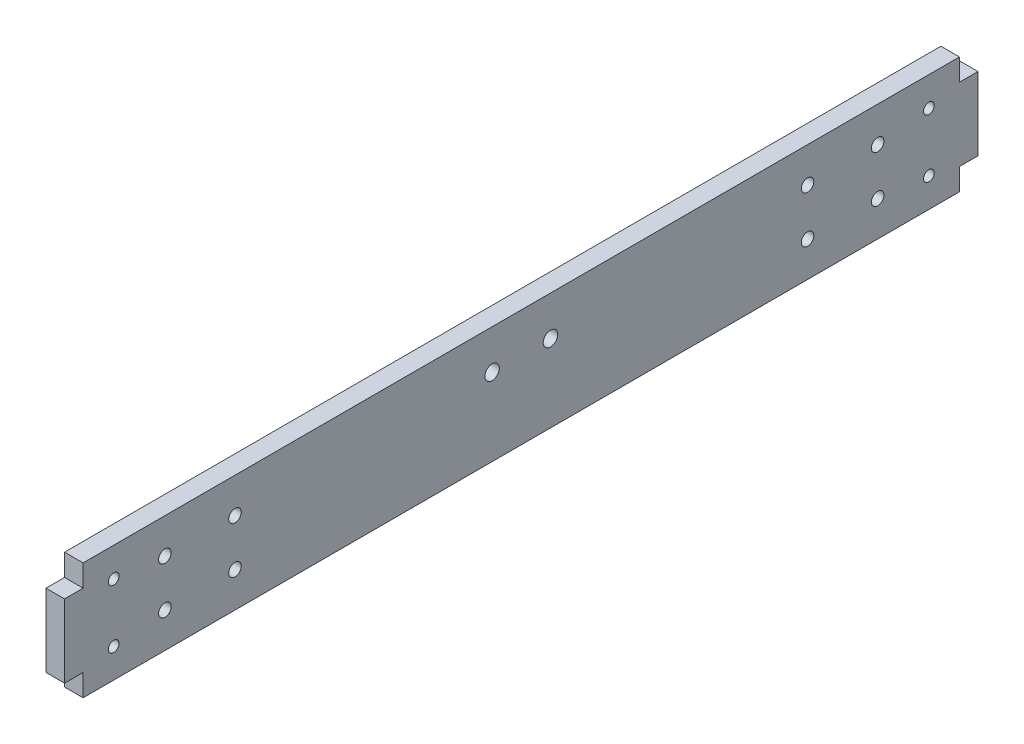
SolidWorks part; units mm, degrees
ref_plane "Front Plane" through (0, 0, 0) normal (0, 0, 1) x (1, 0, 0)
ref_plane "Top Plane" through (0, 0, 0) normal (0, 1, 0) x (1, 0, 0)
ref_plane "Right Plane" through (0, 0, 0) normal (1, 0, 0) x (0, 0, -1)
sketch "Sketch1" plane through (0, 0, 0) normal (1, 0, 0) x (0, 0, -1)
  line L0 (-150, -20) -> (-150, 20)
  line L1 (-150, -20) -> (150, -20)
  line L2 (-150, 20) -> (150, 20)
  line L3 (150, -20) -> (150, 20)
  line L4 (-150, -20) -> (150, 20) construction
  line L5 (-150, 20) -> (150, -20) construction
  point P1 (0, 0)
  dimension "D1" = 300
  dimension "D2" = 40
extrude "Boss-Extrude1" add sketch "Sketch1" along normal blind 6.35
sketch "Sketch2" plane through (6.35, 0, 0) normal (1, 0, 0) x (0, 0, -1)
  line L0 (-156.35, 12.5) -> (-150, 12.5)
  line L1 (-156.35, 12.5) -> (-156.35, -12.5)
  line L2 (-150, 12.5) -> (-150, -12.5)
  line L3 (-156.35, -12.5) -> (-150, -12.5)
  line L4 (-156.35, 12.5) -> (-150, -12.5) construction
  line L5 (-150, 12.5) -> (-156.35, -12.5) construction
  line L6 (156.35, 12.5) -> (150, 12.5)
  line L7 (156.35, 12.5) -> (156.35, -12.5)
  line L8 (150, 12.5) -> (150, -12.5)
  line L9 (156.35, -12.5) -> (150, -12.5)
  line L10 (156.35, 12.5) -> (150, -12.5) construction
  line L11 (150, 12.5) -> (156.35, -12.5) construction
  line L12 (-150, 20) -> (-150, -20) construction
  line L13 (150, -20) -> (150, 20) construction
  point P1 (-153.175, 0)
  point P2 (153.175, 0)
  dimension "D1" = 25
  dimension "D2" = 6.35
extrude "Boss-Extrude2" add sketch "Sketch2" against normal blind 6.35
sketch "Sketch3" plane through (6.35, 0, 0) normal (1, 0, 0) x (0, 0, -1)
  line L0 (10, 6.5) -> (-10, 6.5) construction
  point P3 (0, 6.5)
  dimension "D1" = 20
  dimension "D2" = 6.5
hole_wizard "#10 Clearance Hole1" positions "Sketch5" profile "Sketch4" hole size "#10" standard "ANSI Inch" end condition through all
sketch "Sketch5" plane through (6.35, 0, 0) normal (1, 0, 0) x (0, 0, -1)
  point P0 (-10, 6.5)
  point P3 (10, 6.5)
sketch "Sketch4" plane through (6.35, 6.5, 10) normal (0, 1, 0) x (0, 0, -1)
  line L0 (0, 0) -> (0, 6.35)
  line L1 (0, 6.35) -> (2.4892, 6.35)
  line L2 (2.4892, 6.35) -> (2.4892, 0)
  line L5 (2.4892, 0) -> (0, 0)
  line L11 (0, -6.35) -> (0, 107.95) construction
  dimension "Thru Hole Dia." = 4.9784
  dimension "Thru Hole Depth" = 6.35
sketch "Sketch6" plane through (6.35, 0, 0) normal (1, 0, 0) x (0, 0, -1)
  line L0 (-122, -8) -> (-98, -8) construction
  line L1 (-122, -8) -> (-122, 8) construction
  line L2 (-98, -8) -> (-98, 8) construction
  line L3 (-122, 8) -> (-98, 8) construction
  line L4 (-122, -8) -> (-98, 8) construction
  line L5 (-98, -8) -> (-122, 8) construction
  line L6 (122, -8) -> (122, 8) construction
  line L7 (122, -8) -> (98, -8) construction
  line L8 (122, 8) -> (98, 8) construction
  line L9 (98, -8) -> (98, 8) construction
  line L10 (122, -8) -> (98, 8) construction
  line L11 (122, 8) -> (98, -8) construction
  line L12 (-110, 0) -> (110, 0) construction
  point P1 (-110, 0)
  point P2 (110, 0)
  dimension "D1" = 24
  dimension "D2" = 16
  dimension "D3" = 220
hole_wizard "#8 Clearance Hole1" positions "Sketch8" profile "Sketch7" hole size "#8" standard "ANSI Inch" end condition through all
sketch "Sketch8" plane through (6.35, 0, 0) normal (1, 0, 0) x (0, 0, -1)
  point P0 (-122, 8)
  point P3 (-98, 8)
  point P6 (-98, -8)
  point P9 (-122, -8)
  point P12 (98, 8)
  point P15 (122, 8)
  point P18 (122, -8)
  point P21 (98, -8)
sketch "Sketch7" plane through (6.35, 8, 122) normal (0, 1, 0) x (0, 0, -1)
  line L0 (0, 0) -> (0, 6.35)
  line L1 (0, 6.35) -> (2.1526, 6.35)
  line L2 (2.1526, 6.35) -> (2.1526, 0)
  line L5 (2.1526, 0) -> (0, 0)
  line L11 (0, -6.35) -> (0, 107.95) construction
  dimension "Thru Hole Dia." = 4.3053
  dimension "Thru Hole Depth" = 6.35
sketch "Sketch9" plane through (6.35, 0, 0) normal (1, 0, 0) x (0, 0, -1)
  line L1 (-139.5352, 10) -> (-139.5352, -10) construction
  line L2 (139.5352, 10) -> (139.5352, -10) construction
  line L3 (-150, 20) -> (-150, 12.5) construction
  line L4 (150, 12.5) -> (150, 20) construction
  point P4 (0, 0)
  point P5 (-139.5352, 0)
  point P7 (139.5352, 0)
  dimension "D1" = 20
  dimension "D2" = 10.4648
  dimension "D3" = 10.4648
hole_wizard "#6 Clearance Hole1" positions "3DSketch1" profile "Sketch10" hole size "#6" standard "ANSI Inch" end condition through all
sketch3d "3DSketch1"
  point P0 (6.35, 10, 139.5352)
  point P3 (6.35, -10, 139.5352)
  point P6 (6.35, 10, -139.5352)
  point P9 (6.35, -10, -139.5352)
sketch "Sketch10" plane through (6.35, 10, 139.5352) normal (0, 1, 0) x (0, 0, -1)
  line L0 (0, 0) -> (0, 6.35)
  line L1 (0, 6.35) -> (1.8288, 6.35)
  line L2 (1.8288, 6.35) -> (1.8288, 0)
  line L5 (1.8288, 0) -> (0, 0)
  line L11 (0, -6.35) -> (0, 107.95) construction
  dimension "Thru Hole Dia." = 3.6576
  dimension "Thru Hole Depth" = 6.35
